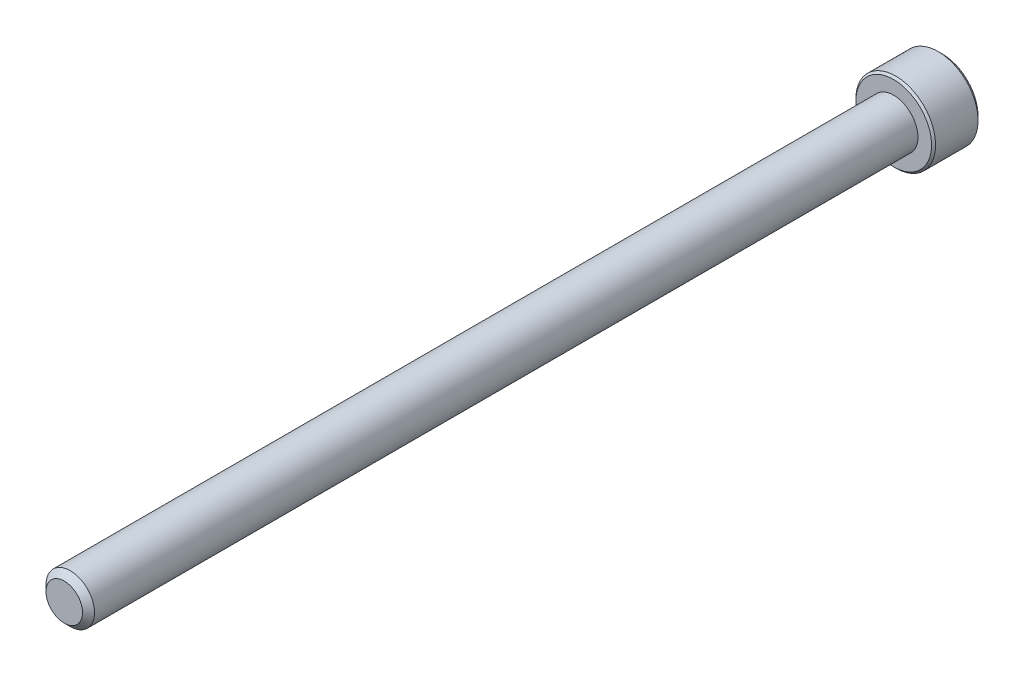
SolidWorks part; units mm, degrees
ref_plane "Front Plane" through (0, 0, 0) normal (0, 0, 1) x (1, 0, 0)
ref_plane "Top Plane" through (0, 0, 0) normal (0, 1, 0) x (1, 0, 0)
ref_plane "Right Plane" through (0, 0, 0) normal (1, 0, 0) x (0, 0, -1)
sketch "Sketch0" plane through (0, 0, 0) normal (1, 0, 0) x (0, 0, -1)
  line L0 (0, 0) -> (82.55, 0) construction
  line L1 (0, -2.413) -> (0, 2.413) construction
  line L2 (87.376, -3.9688) -> (87.376, 3.9687) construction
  line L3 (87.376, -1.9844) -> (87.376, 1.9844) construction
  point P2 (87.376, 0)
  point P4 (22.225, 0)
  point P8 (0, 0)
  point P11 (87.376, 0)
  point P14 (87.376, 0)
  dimension "Min Thread" = 22.225
  dimension "OD" = 4.826
  dimension "screw length" = 82.55
  dimension "head depth" = 4.826
  dimension "head dia" = 7.9375
  dimension "hex dia" = 3.9688
sketch "Sketch1" plane through (0, 0, 0) normal (0, 0, 1) x (1, 0, 0)
  circle A0 centre (0, 0) radius 2.413
  dimension "OD" = 4.826
extrude "Extrude1" add sketch "Sketch1" against normal blind 82.55
sketch "Sketch2" [suppressed] plane through (0, 0, 0) normal (0, 0, 1) x (1, 0, 0)
  circle A0 centre (0, 0) radius 2.413 construction
  circle A1 centre (0, 0) radius 2.413
chamfer "Chamfer3" distance 0.5953 angle 45 1 edges at (2.413, 0, 0)
sketch "Sketch3" [suppressed] plane through (0, 0, 0) normal (1, 0, 0) x (0, 0, -1)
  line L0 (-0.6945, 2.413) -> (-0.3969, 1.8974)
  line L1 (-0.3969, 1.8974) -> (-0.2977, 1.8974)
  line L2 (-0.2977, 1.8974) -> (0, 2.413)
  line L3 (-0.6945, 2.413) -> (0, 2.413)
  line L4 (-0.3473, 2.413) -> (-0.3473, 1.8974) construction
  line L5 (-0.5457, 2.1552) -> (-0.1488, 2.1552) construction
  line L6 (0, 2.413) -> (0, -2.413) construction
  dimension "D1" = 0.0992
  dimension "D2" = 0.3969
  dimension "D3" = 60
sketch "Sketch6" plane through (0, 0, -82.55) normal (0, 0, -1) x (-1, 0, 0)
  circle A0 centre (0, 0) radius 3.9688
  dimension "head dia" = 7.9375
extrude "Extrude2" add sketch "Sketch6" along normal blind 4.826
sketch "Sketch7" plane through (0, 0, -87.376) normal (0, 0, -1) x (-1, 0, 0)
  line L1 (0, 2.2914) -> (-1.9844, 1.1457)
  line L2 (-1.9844, 1.1457) -> (-1.9844, -1.1457)
  line L3 (-1.9844, -1.1457) -> (0, -2.2914)
  line L4 (0, -2.2914) -> (1.9844, -1.1457)
  line L5 (1.9844, -1.1457) -> (1.9844, 1.1457)
  line L6 (1.9844, 1.1457) -> (0, 2.2914)
  circle A0 centre (0, 0) radius 1.9844 construction
  dimension "hex dia" = 3.9688
extrude "Cut-Extrude1" cut sketch "Sketch7" against normal blind 2.9766
sketch "Sketch8" plane through (0, 0, -87.376) normal (0, 0, -1) x (-1, 0, 0)
  circle A0 centre (0, 0) radius 2.2914
extrude "Cut-Extrude2" cut sketch "Sketch8" against normal through all draft 45
chamfer "Chamfer1" distance 0.3969 angle 45 1 edges at (-3.9688, 0, -87.376)
chamfer "Chamfer2" distance 0.1984 angle 45 1 edges at (-3.9688, 0, -82.55)
sketch "Sketch9" plane through (0, 0, 0) normal (1, 0, 0) x (0, 0, -1)
  line L0 (87.376, -3.9688) -> (87.376, 3.9688) construction
  line L2 (82.55, -3.9688) -> (82.55, 3.9687) construction
  line L9 (86.9791, 3.9688) -> (82.7484, 3.9688) construction
  line L10 (0, -2.413) -> (0, 2.413) construction
  line L11 (0, -2.413) -> (0, 2.413)
  line L12 (1.9844, -2.413) -> (1.9844, 2.413) construction
  point P4 (87.376, 0)
  point P6 (82.55, 0)
  point P14 (1.9844, 0)
  point P15 (1.9844, -2.413)
  dimension "D1" = 1.9844
ref_plane "Contact Plane 1" through (0, 0, -82.55) normal (0, 0, 1) x (1, 0, 0)
ref_axis "Center Axis 1" through (0, 0, 9.7485) along (0, 0, -1)
curve "Helix/Spiral1" [suppressed] pitch 0.7937 height 83.3438 turns 105 parameters "pitch"=0.7937
sweep "Cut-Sweep1" [suppressed] cut profiles "Sketch3" path "Helix/Spiral1"
sketch "Sketch5" [suppressed] plane through (0, 0, 0) normal (1, 0, 0) x (0, 0, -1)
  line L1 (82.5754, 2.413) -> (22.225, 2.413)
  line L2 (82.5754, 2.413) -> (82.5754, 0)
  line L3 (82.5754, 0) -> (21.3467, 0)
  line L4 (0, 0) -> (82.55, 0) construction
  line L5 (22.225, 2.413) -> (21.3467, 0)
  line L6 (0, 0) -> (87.376, 0) construction
  dimension "D1" = 70
  dimension "D3" = 4.8006
revolve "partially thread" [suppressed] add sketch "Sketch5" angle 360 about L6
sketch "Sketch10" [suppressed] plane through (0, 0, -82.55) normal (0, 0, 1) x (1, 0, 0)
  line L0 (-0.4271, 4.1672) -> (0, 3.7703)
  line L1 (0, 3.7703) -> (0.4271, 4.1672)
  line L2 (0, 3.7703) -> (0, 4.1672) construction
  line L3 (-0.4271, 4.1672) -> (0.4271, 4.1672)
  line L4 (0, -6.5395) -> (0, 6.5395) construction
  line L5 (0, 0) -> (0.2077, 3.9633) construction
  line L6 (-0.2077, 3.9633) -> (0, 0) construction
  circle A2 centre (0, 0) radius 3.9688 construction
  circle A5 centre (0, 0) radius 3.7703 construction
  dimension "D2" = 0.3969
  dimension "D1" = 6
extrude "Cut-Extrude3" [suppressed] cut sketch "Sketch10" against normal through all
pattern_circular "CirPattern1" [suppressed] count 60 over 360 of bodies 108
equation "\"D3@Helix/Spiral1\"=\"pitch@Helix/Spiral1\"+\"screw length@Sketch0\""
equation "\"D1@Sketch3\" = \"pitch@Helix/Spiral1\"*.125"
equation "\"D2@Sketch3\" = \"pitch@Helix/Spiral1\"*.5"
equation "\"D1@Cut-Extrude1\"=\"hex dia@Sketch0\"*.75"
equation "\"D1@Chamfer1\"=\"head dia@Sketch0\"*.05"
equation "\"D1@Chamfer2\" = \"D1@Chamfer1\"/2"
equation "\"D1@Chamfer3\" = \"pitch@Helix/Spiral1\"*.750"
equation "\"D2@Sketch10\"=\"D1@Chamfer1\""
equation "\"D1@CirPattern1\"=\"D3@CirPattern1\"/\"D1@Sketch10\""
equation "\"D1@Sketch9\"=\"pitch@Helix/Spiral1\"*2.5"
equation "\"OD@Sketch1\"=\"OD@Sketch0\""
equation "\"screw length@Extrude1\"=\"screw length@Sketch0\""
equation "\"head depth@Extrude2\"=\"head depth@Sketch0\""
equation "\"head dia@Sketch6\"=\"head dia@Sketch0\""
equation "\"hex dia@Sketch7\"=\"hex dia@Sketch0\""
equation "\"D3@Sketch5\"=\"head depth@Sketch0\"-.001"
